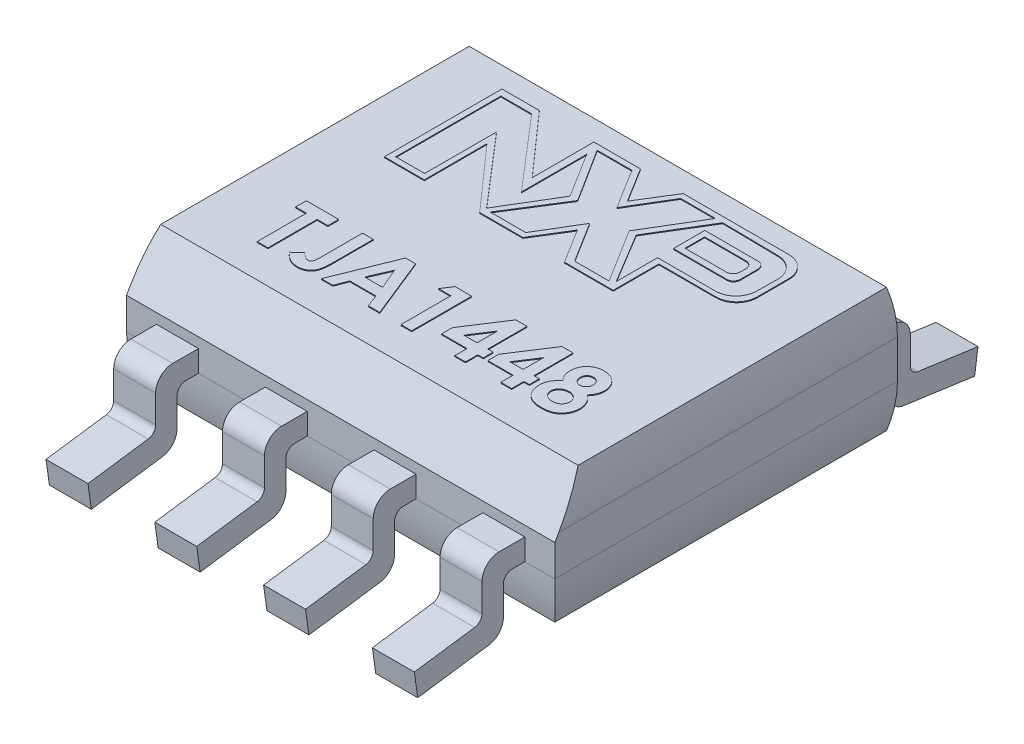
SolidWorks part; units mm, degrees
ref_plane "Front Plane" through (0, 0, 0) normal (0, 0, 1) x (1, 0, 0)
ref_plane "Top Plane" through (0, 0, 0) normal (0, 1, 0) x (1, 0, 0)
ref_plane "Right Plane" through (0, 0, 0) normal (1, 0, 0) x (0, 0, -1)
sketch "Sketch1" plane through (0, 0, 0) normal (0, 1, 0) x (1, 0, 0)
  line L1 (-2.5, 2) -> (2.5, 2)
  line L2 (-2.5, 2) -> (-2.5, -2)
  line L3 (-2.5, -2) -> (2.5, -2)
  line L4 (2.5, 2) -> (2.5, -2)
  line L5 (-2.5, 2) -> (2.5, -2) construction
  line L6 (-2.5, -2) -> (2.5, 2) construction
  point P0 (0, 0)
  dimension "D1" = 5
  dimension "D2" = 4
extrude "Boss-Extrude1" add sketch "Sketch1" along normal blind 1.45
sketch "Sketch2" plane through (-2.5, 0, 0) normal (-1, 0, 0) x (0, 0, 1)
  line L0 (2, 0.8687) -> (1.6644, 1.45)
  line L1 (2, 1.45) -> (2, 0) construction
  line L2 (-2, 1.45) -> (2, 1.45) construction
  line L3 (0, 0) -> (0, 0.828) construction
  line L4 (-2, 0.725) -> (-1.3983, 0.725) construction
  line L6 (-2, 1.45) -> (-2, 0) construction
  line L7 (-1.8644, 1.6723) -> (-2.1559, 1.6723)
  line L8 (-2.1559, 1.6723) -> (-2.1559, 0.954)
  line L9 (-2.1559, 0.954) -> (-2, 0.9484)
  line L10 (-2, 0.5016) -> (-2.1559, 0.5016)
  line L11 (-2.1559, 0.5016) -> (-2.1559, -0.2223)
  line L12 (-2.1559, -0.2223) -> (-1.8644, -0.2223)
  line L13 (1.6644, 1.45) -> (1.6644, 1.7317)
  line L14 (1.6644, 1.7317) -> (2.4871, 1.7317)
  line L15 (2.4871, 1.7317) -> (2.4871, 0.8687)
  line L16 (2.4871, 0.8687) -> (2, 0.8687)
  line L17 (2, 0.5015) -> (2.4871, 0.5015)
  line L18 (2.4871, 0.5015) -> (2.4871, -0.2223)
  line L19 (2.4871, -0.2223) -> (1.8644, -0.2223)
  arc A0 (2, 0.5015) -> (1.8644, -0.2223) centre (0, 0.5015) cw
  arc A1 (-2, 0.5016) -> (-1.8644, -0.2223) centre (0, 0.5015) ccw
  arc A2 (-2, 0.9484) -> (-1.8644, 1.6723) centre (0, 0.9485) cw
  dimension "D1" = 2
  dimension "D2" = 60
extrude "Cut-Extrude1" cut sketch "Sketch2" against normal blind 61.45
sketch "Sketch5" plane through (0, 0, -2) normal (0, 0, -1) x (-1, 0, 0)
  line L1 (0, 1.45) -> (0, 1.0867) construction
  line L2 (-3.4587, 0.725) -> (-2.857, 0.725) construction
  line L3 (-2.3644, 1.6723) -> (-2.6559, 1.6723)
  line L4 (-2.6559, 1.6723) -> (-2.6559, 0.954)
  line L5 (-2.6559, 0.954) -> (-2.5, 0.9484)
  line L6 (-2.5, 0.5016) -> (-2.6559, 0.5016)
  line L7 (-2.6559, 0.5016) -> (-2.6559, -0.2223)
  line L8 (-2.6559, -0.2223) -> (-2.3644, -0.2223)
  line L16 (2.5, 1.45) -> (-2.5, 1.45) construction
  line L17 (-2.6559, 1.6723) -> (-2.3644, 1.6723)
  line L18 (-2.6559, 0.9484) -> (-2.6559, 1.6723)
  line L19 (-2.5, 0.9484) -> (-2.6559, 0.9484)
  line L20 (-2.6559, 0.496) -> (-2.5, 0.5016)
  line L21 (-2.6559, -0.2223) -> (-2.6559, 0.496)
  line L22 (-2.3644, -0.2223) -> (-2.6559, -0.2223)
  line L23 (2.6559, -0.2223) -> (2.3644, -0.2223)
  line L24 (2.6559, 0.5016) -> (2.6559, -0.2223)
  line L25 (2.5, 0.5016) -> (2.6559, 0.5016)
  line L26 (2.6559, 0.954) -> (2.5, 0.9484)
  line L27 (2.6559, 1.6723) -> (2.6559, 0.954)
  line L28 (2.3644, 1.6723) -> (2.6559, 1.6723)
  arc A1 (-2.5, 0.5016) -> (-2.3644, -0.2223) centre (-0.5, 0.5015) ccw
  arc A2 (-2.5, 0.9484) -> (-2.3644, 1.6723) centre (-0.5, 0.9485) cw
  arc A3 (-2.5, 0.5016) -> (-2.3644, -0.2223) centre (-0.5, 0.5015) ccw
  arc A4 (-2.5, 0.9484) -> (-2.3644, 1.6723) centre (-0.5, 0.9485) cw
  arc A5 (2.5, 0.5016) -> (2.3644, -0.2223) centre (0.5, 0.5015) cw
  arc A6 (2.5, 0.9484) -> (2.3644, 1.6723) centre (0.5, 0.9485) ccw
extrude "Cut-Extrude2" cut sketch "Sketch5" against normal blind 61.45 contours L5 A2 L3 L4 | A1 L20 L7 L22 | A6 L26 L27 L28 | L25 A5 L23 L24
sketch "Sketch6" plane through (-2.5, 0, 0) normal (-1, 0, 0) x (0, 0, 1)
  line L5 (1.9361, 0) -> (-1.9361, 0) construction
  line L7 (0, 0) -> (0, -0.7239) construction
  line L8 (2.2535, 0.75) -> (2.3, 0.75)
  line L9 (2.5, 0.55) -> (2.5, 0.2276)
  line L10 (2.5, 0.1406) -> (3.25, 0.1406) construction
  line L11 (3.25, 0.1406) -> (3.25, -0.1094) construction
  line L12 (3.25, -0.1094) -> (2.25, -0.1094) construction
  line L13 (2.25, 0.0645) -> (2.25, 0.4)
  line L14 (2.25, 0.5) -> (2.2535, 0.5)
  line L15 (-3.25, -0.1094) -> (-2.25, -0.1094) construction
  line L17 (2.4222, -0.1335) -> (3.2508, -0.25)
  line L18 (2.5861, 0.1286) -> (3.2901, 0.0296)
  line L19 (3.2508, -0.25) -> (3.2901, 0.0296)
  line L20 (-3.25, 0.1406) -> (-3.25, -0.1094) construction
  line L21 (-2.5, 0.1406) -> (-3.25, 0.1406) construction
  line L22 (-3.2508, -0.25) -> (-3.2901, 0.0296)
  line L23 (-2.5861, 0.1286) -> (-3.2901, 0.0296)
  line L24 (-2.4222, -0.1335) -> (-3.2508, -0.25)
  line L25 (-2.25, 0.5) -> (-2.2535, 0.5)
  line L26 (-2.25, 0.0645) -> (-2.25, 0.4)
  line L27 (-2.5, 0.55) -> (-2.5, 0.2276)
  line L28 (-2.2535, 0.75) -> (-2.3, 0.75)
  line L29 (-2.15, 0.5) -> (2.15, 0.5)
  line L30 (-2.2535, 0.75) -> (2.2535, 0.75)
  arc A0 (2.4222, -0.1335) -> (2.25, 0.0645) centre (2.45, 0.0645) cw
  arc A1 (2.5, 0.55) -> (2.3, 0.75) centre (2.3, 0.55) ccw
  arc A2 (2.5861, 0.1286) -> (2.5, 0.2276) centre (2.6, 0.2276) cw
  arc A3 (2.25, 0.4) -> (2.15, 0.5) centre (2.15, 0.4) ccw
  arc A4 (-2.25, 0.4) -> (-2.15, 0.5) centre (-2.15, 0.4) cw
  arc A5 (-2.5861, 0.1286) -> (-2.5, 0.2276) centre (-2.6, 0.2276) ccw
  arc A6 (-2.5, 0.55) -> (-2.3, 0.75) centre (-2.3, 0.55) cw
  arc A7 (-2.4222, -0.1335) -> (-2.25, 0.0645) centre (-2.45, 0.0645) ccw
  dimension "D9" = 0.2
  dimension "D10" = 0.1
  dimension "D4" = 0.25
  dimension "D5" = 0.25
  dimension "D6" = 1
  dimension "D7" = 8
  dimension "D8" = 0.25
extrude "Boss-Extrude2" add sketch "Sketch6" against normal up to surface (5 mm away) up to face at (2.5, 0.8431, 0.3908)
sketch "Sketch7" plane through (0, 1.45, 0) normal (0, 1, 0) x (1, 0, 0)
  line L0 (2.5, -2) -> (-2.5, -2) construction
  line L1 (-2.5, -2) -> (-2.15, -2)
  line L2 (-2.5, -2) -> (-2.5, -3.534)
  line L3 (-2.5, -3.534) -> (-2.15, -3.534)
  line L4 (-2.15, -2) -> (-2.15, -3.534)
  line L5 (-1.66, -2) -> (-0.88, -2)
  line L6 (-1.66, -2) -> (-1.66, -3.6106)
  line L7 (-1.66, -3.6106) -> (-0.88, -3.6106)
  line L8 (-0.88, -2) -> (-0.88, -3.6106)
  line L9 (0, 0) -> (-3.4858, 0) construction
  line L10 (-0.39, -2) -> (0.39, -2)
  line L11 (-0.39, -2) -> (-0.39, -3.6106)
  line L12 (-0.39, -3.6106) -> (0.39, -3.6106)
  line L13 (0.39, -2) -> (0.39, -3.6106)
  line L14 (2.5, -2) -> (2.15, -2)
  line L15 (2.5, -2) -> (2.5, -3.783)
  line L16 (2.5, -3.783) -> (2.15, -3.783)
  line L17 (2.15, -2) -> (2.15, -3.783)
  line L18 (1.66, -2) -> (0.88, -2)
  line L19 (1.66, -2) -> (1.66, -3.6776)
  line L20 (1.66, -3.6776) -> (0.88, -3.6776)
  line L21 (0.88, -2) -> (0.88, -3.6776)
  line L22 (0.88, 2) -> (0.88, 3.6776)
  line L23 (1.66, 3.6776) -> (0.88, 3.6776)
  line L24 (1.66, 2) -> (1.66, 3.6776)
  line L25 (1.66, 2) -> (0.88, 2)
  line L26 (2.15, 2) -> (2.15, 3.783)
  line L27 (2.5, 3.783) -> (2.15, 3.783)
  line L28 (2.5, 2) -> (2.5, 3.783)
  line L29 (2.5, 2) -> (2.15, 2)
  line L30 (0.39, 2) -> (0.39, 3.6106)
  line L31 (-0.39, 3.6106) -> (0.39, 3.6106)
  line L32 (-0.39, 2) -> (-0.39, 3.6106)
  line L33 (-0.39, 2) -> (0.39, 2)
  line L34 (-0.88, 2) -> (-0.88, 3.6106)
  line L35 (-1.66, 3.6106) -> (-0.88, 3.6106)
  line L36 (-1.66, 2) -> (-1.66, 3.6106)
  line L37 (-1.66, 2) -> (-0.88, 2)
  line L38 (-2.15, 2) -> (-2.15, 3.534)
  line L39 (-2.5, 3.534) -> (-2.15, 3.534)
  line L40 (-2.5, 2) -> (-2.5, 3.534)
  line L41 (-2.5, 2) -> (-2.15, 2)
  dimension "D1" = 0.49
  dimension "D2" = 0.49
  dimension "D3" = 0.49
  dimension "D4" = 0.49
  dimension "D5" = 0.78
  dimension "D6" = 0.78
  dimension "D7" = 0.78
  dimension "D8" = 0.35
extrude "Cut-Extrude3" cut sketch "Sketch7" against normal blind 61.45
sketch "Sketch8" plane through (0, 1.45, 0) normal (0, 1, 0) x (1, 0, 0)
  line L0 (70.6653, 255.7964) -> (518.6653, 255.7964) construction
  line L1 (-1.8034, 0.3139) -> (-1.8034, 1.6861)
  line L2 (-1.8034, 1.6861) -> (-1.3672, 1.6861)
  line L3 (-1.3672, 1.6861) -> (-0.7295, 0.965)
  line L4 (-0.7295, 0.965) -> (-0.7295, 1.6861)
  line L5 (-0.7295, 1.6861) -> (-0.186, 1.6861)
  line L6 (-0.186, 1.6861) -> (0.0636, 1.2836)
  line L7 (0.0636, 1.2836) -> (0.3123, 1.6861)
  line L8 (0.3123, 1.6861) -> (1.5487, 1.6861)
  line L9 (1.7887, 1.4461) -> (1.7887, 1.0732)
  line L10 (1.5487, 0.8332) -> (0.8817, 0.8332)
  line L11 (0.8817, 0.8332) -> (0.8817, 0.2999)
  line L12 (0.8817, 0.2999) -> (0.3123, 0.2999)
  line L13 (0.3123, 0.2999) -> (0.0636, 0.7007)
  line L14 (0.0636, 0.7007) -> (-0.1796, 0.3069)
  line L15 (-0.1796, 0.3069) -> (-0.6842, 0.3069)
  line L16 (-0.6842, 0.3069) -> (-1.3377, 1.046)
  line L17 (-1.3377, 1.046) -> (-1.3377, 0.3139)
  line L18 (-1.3377, 0.3139) -> (-1.8034, 0.3139)
  line L19 (-1.7377, 0.3801) -> (-1.7377, 1.6079)
  line L20 (-1.7377, 1.6079) -> (-1.3789, 1.6079)
  line L21 (-1.3789, 1.6079) -> (-0.6481, 0.759)
  line L22 (-0.6481, 0.759) -> (-0.6481, 1.5221)
  line L23 (-0.6481, 1.5221) -> (-0.3221, 0.9996)
  line L24 (-0.3221, 0.9996) -> (-0.6875, 0.3914)
  line L25 (-0.6875, 0.3914) -> (-1.3999, 1.219)
  line L26 (-1.3999, 1.219) -> (-1.3999, 0.3801)
  line L27 (-1.3999, 0.3801) -> (-1.7377, 0.3801)
  line L28 (-0.6279, 1.6222) -> (-0.2222, 1.6222)
  line L29 (-0.2222, 1.6222) -> (0.068, 1.1578)
  line L30 (0.068, 1.1578) -> (0.3464, 1.6222)
  line L31 (0.3464, 1.6222) -> (0.7514, 1.6222)
  line L32 (0.7514, 1.6222) -> (0.3743, 0.9932)
  line L33 (0.3743, 0.9932) -> (0.7643, 0.369)
  line L34 (0.7643, 0.369) -> (0.3619, 0.369)
  line L35 (0.3619, 0.369) -> (0.068, 0.8394)
  line L36 (0.068, 0.8394) -> (-0.2117, 0.373)
  line L37 (-0.2117, 0.373) -> (-0.6279, 0.373)
  line L38 (-0.6279, 0.373) -> (-0.2334, 0.9996)
  line L39 (-0.2334, 0.9996) -> (-0.6279, 1.6222)
  line L40 (0.8381, 1.6222) -> (1.4939, 1.613)
  line L41 (1.7305, 1.3696) -> (1.727, 1.1248)
  line L42 (1.4871, 0.8882) -> (0.8112, 0.8882)
  line L43 (0.8112, 0.8882) -> (0.8112, 0.4059)
  line L44 (0.8112, 0.4059) -> (0.4571, 0.9932)
  line L45 (0.4571, 0.9932) -> (0.8381, 1.6222)
  line L46 (0.8112, 1.4396) -> (1.433, 1.4396)
  line L47 (1.513, 1.3596) -> (1.513, 1.1532)
  line L48 (1.433, 1.0732) -> (0.8112, 1.0732)
  line L49 (0.8112, 1.4396) -> (0.8112, 1.0732)
  line L50 (0.8755, 1.3732) -> (1.3583, 1.3732)
  line L51 (0.8755, 1.3732) -> (0.8755, 1.144)
  line L52 (0.8755, 1.144) -> (1.3583, 1.144)
  line L53 (1.4383, 1.2932) -> (1.4383, 1.224)
  arc A0 (1.7887, 1.0732) -> (1.5487, 0.8332) centre (1.5487, 1.0732) cw
  arc A1 (1.5487, 1.6861) -> (1.7887, 1.4461) centre (1.5487, 1.4461) cw
  arc A2 (1.727, 1.1248) -> (1.4871, 0.8882) centre (1.4871, 1.1282) cw
  arc A3 (1.4939, 1.613) -> (1.7305, 1.3696) centre (1.4905, 1.373) cw
  arc A4 (1.3583, 1.144) -> (1.4383, 1.224) centre (1.3583, 1.224) ccw
  arc A5 (1.3583, 1.3732) -> (1.4383, 1.2932) centre (1.3583, 1.2932) cw
  arc A6 (1.513, 1.1532) -> (1.433, 1.0732) centre (1.433, 1.1532) cw
  arc A7 (1.433, 1.4396) -> (1.513, 1.3596) centre (1.433, 1.3596) cw
extrude "Boss-Extrude3" add sketch "Sketch8" along normal blind 0.01 contours A1 L8 L7 L6 L5 L4 L3 L2 L1 L18 L17 L16 L15 L14 L13 L12 L11 L10 A0 L9 L38 L39 L28 L29 L30 L31 L32 L33 L34 L35 L36 L37 L26 L27 L19 L20 L21 L22 L23 L24 L25 L40 A3 L41 A2 L42 L43 L44 | A7 L46 L49 L48 A6 L47 L50 A5 L53 A4 L52 L51
sketch "Sketch9" plane through (0, 1.45, 0) normal (0, 1, 0) x (1, 0, 0)
  line L0 (-1.8233, -1.2861) -> (2.2013, -1.2861) construction
  text T0 "<b>TJA1448</b>" font "Century Gothic" height 0.7
extrude "Boss-Extrude4" add sketch "Sketch9" along normal blind 0.01
